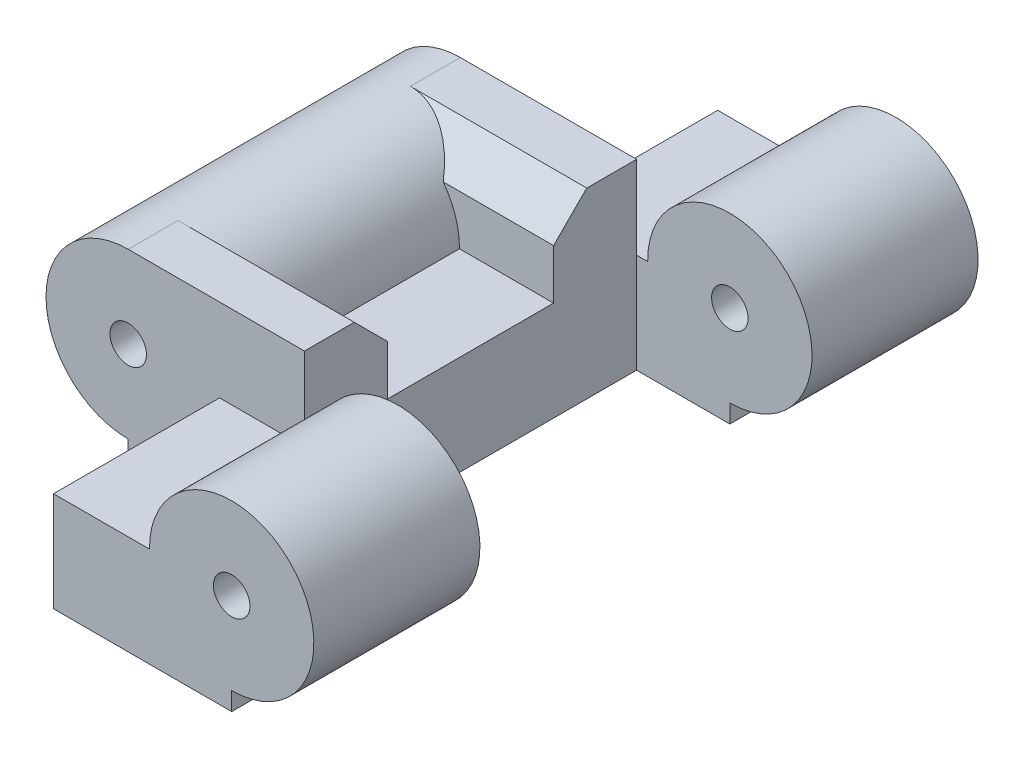
SolidWorks part; units mm, degrees
ref_plane "Front Plane" through (0, 0, 0) normal (0, 0, 1) x (1, 0, 0)
ref_plane "Top Plane" through (0, 0, 0) normal (0, 1, 0) x (1, 0, 0)
ref_plane "Right Plane" through (0, 0, 0) normal (1, 0, 0) x (0, 0, -1)
sketch "Sketch1" plane through (0, 0, 0) normal (0, 1, 0) x (1, 0, 0)
  line L0 (0, 0) -> (10.6165, 0) construction
  line L1 (10.6165, 10) -> (0, 10)
  line L2 (10.6165, 10) -> (10.6165, -10)
  line L3 (10.6165, -10) -> (0, -10)
  line L4 (0, 10) -> (0, -10)
  line L5 (5.5005, -10) -> (16.2325, -10)
  line L6 (5.5005, -10) -> (5.5005, -20)
  line L7 (5.5005, -20) -> (16.2325, -20)
  line L8 (16.2325, -10) -> (16.2325, -20)
  line L13 (5.5005, 20) -> (16.2325, 20)
  line L14 (16.2325, 10) -> (16.2325, 20)
  line L15 (5.5005, 10) -> (16.2325, 10)
  line L16 (5.5005, 10) -> (5.5005, 20)
  point P4 (0, 0)
  dimension "D1" = 10.732
  dimension "D2" = 10.6165
  dimension "D3" = 5.116
  dimension "D4" = 10
  dimension "D5" = 20
extrude "Boss-Extrude1" add sketch "Sketch1" along normal blind 6 contours L8 L5 L3 L6 L7 | L0 L4 L3 L2 | L4 L0 L2 L1 | L16 L1 L15 L14 L13 region at (5.3083, 0, -5) region at (5.3083, 0, 5) region at (10.8665, 0, -15) region at (10.8665, 0, 15)
sketch "Sketch2" plane through (0, 6, 0) normal (0, 1, 0) x (1, 0, 0)
  line L0 (10.6165, 10) -> (10.6165, -10) construction
  line L1 (0, 10) -> (0, -10) construction
  line L2 (10.6165, 10) -> (10.6165, 5)
  line L3 (0, 10) -> (0, 5)
  line L4 (10.6165, -10) -> (0, -10)
  line L5 (10.6165, 10) -> (0, 10)
  line L6 (10.6165, -5) -> (0, -5)
  line L7 (0, 0) -> (10.6165, 0) construction
  line L8 (10.6165, 5) -> (0, 5)
  line L9 (0, -5) -> (0, -10)
  line L10 (10.6165, -5) -> (10.6165, -10)
  point P11 (10.6165, 0)
  dimension "D1" = 5
extrude "Boss-Extrude2" add sketch "Sketch2" along normal blind 5
chamfer "Chamfer1" distance 2 2 edges at (5.3083, 11, -5) (5.3083, 11, 5)
ref_plane "Plane1" through (0, 0, 0) normal (0, 0, 1) x (1, 0, 0)
sketch "Sketch3" plane through (0, 0, 0) normal (0, 0, 1) x (1, 0, 0)
  line L0 (0, 11) -> (0, 0) construction
  line L1 (5.5005, 0) -> (0, 0) construction
  line L2 (5.5005, 0) -> (0, 0) construction
  line L3 (0, 11) -> (10.6165, 11) construction
  line L4 (0, 11) -> (10.6165, 11) construction
  line L5 (16.2325, 6) -> (16.2325, 0) construction
  line L6 (16.2325, 6) -> (16.2325, 0)
  circle A0 centre (0, 6.05) radius 4.95
  circle A1 centre (16.2325, 6.05) radius 4.95
  point P4 (0, 1.1)
  point P7 (0, 11)
  point P14 (0, 0)
  point P15 (16.2325, 1.1)
  point P16 (0, 0)
  dimension "D1" = 1.1
extrude "Boss-Extrude3" add sketch "Sketch3" along normal up to surface (10 mm away) from surface contours A0 region at (0, 6.05, 0) up to face at (5.3723, 5.6667, 10) starting at face at (5.3723, 5.6667, -10)
extrude "Boss-Extrude4" add sketch "Sketch3<3>" along normal up to surface (20 mm away) from surface contours A1 region at (16.2325, 6.05, 0) up to face at (10.8665, 3, 20) starting at face at (13.4245, 3, 10)
sketch "Sketch3<3>" plane through (0, 0, 0) normal (0, 0, 1) x (1, 0, 0) same geometry as "Sketch3"
extrude "Boss-Extrude5" add sketch "Sketch3<4>" along normal up to surface (-10 mm away) from surface contours A1 region at (16.2325, 6.05, 0) up to face at (13.4245, 3, -10) starting at face at (10.8665, 3, -20)
sketch "Sketch3<4>" plane through (0, 0, 0) normal (0, 0, 1) x (1, 0, 0) same geometry as "Sketch3"
sketch "Sketch6" plane through (0, 0, 20) normal (0, 0, 1) x (1, 0, 0)
  arc A0 (0, 11) -> (0, 1.1) centre (0, 6.05) ccw construction
  arc A1 (16.2325, 1.1) -> (11.2828, 6) centre (16.2325, 6.05) ccw construction
  arc A2 (0, 11) -> (0, 1.1) centre (0, 6.05) ccw construction
  arc A3 (16.2325, 1.1) -> (11.2828, 6) centre (16.2325, 6.05) ccw construction
sketch "Sketch7" plane through (0, 0, 20) normal (0, 0, 1) x (1, 0, 0)
  point P0 (0, 6.05)
  point P3 (16.2325, 6.05)
hole_wizard "Ø1.0mm Dowel Hole1" positions "Sketch7" profile "Sketch8" hole size "Ø1.0" standard "ANSI Metric" end condition through all
sketch "Sketch8" plane through (0, 6.05, 20) normal (1, 0, 0) x (0, -1, 0)
  line L0 (0, 0) -> (0, 40)
  line L1 (0, 40) -> (1.1, 40)
  line L2 (1.1, 40) -> (1.1, 0)
  line L5 (1.1, 0) -> (0, 0)
  line L11 (0, -6.35) -> (0, 107.95) construction
  dimension "Thru Hole Dia." = 2.2
  dimension "Thru Hole Depth" = 40
